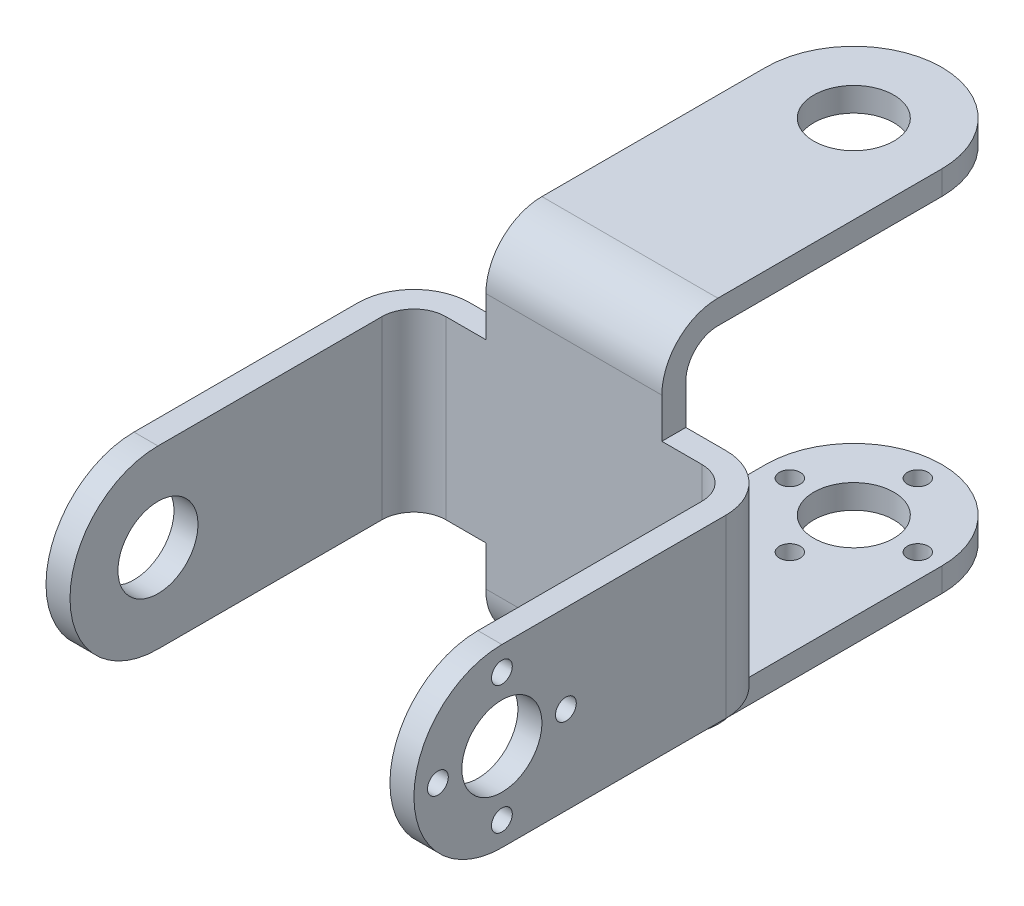
SolidWorks part; units mm, degrees
ref_plane "Front Plane" through (0, 0, 0) normal (0, 0, 1) x (1, 0, 0)
ref_plane "Top Plane" through (0, 0, 0) normal (0, 1, 0) x (1, 0, 0)
ref_plane "Right Plane" through (0, 0, 0) normal (1, 0, 0) x (0, 0, -1)
sketch "Sketch1" plane through (0, 0, 0) normal (0, 1, 0) x (1, 0, 0)
  line L1 (-11, 0) -> (11, 0)
  line L2 (-11, 0) -> (-11, -28)
  line L3 (-11, -28) -> (11, -28)
  line L4 (11, 0) -> (11, -28)
  circle A0 centre (0, 0) radius 11
  circle A2 centre (0, 0) radius 5
  dimension "D3" = 22
  dimension "D4" = 10
  dimension "D5" = 28
extrude "Boss-Extrude1" add sketch "Sketch1" along normal blind 3 contours L1 A2 A0 | L1 A0 A2 | A0 L2 L3 L4 region at (0, 0, -5.3317) region at (0, 0, 5.3317) region at (0, 0, 18.164)
sketch "Sketch2" plane through (11, 0, 0) normal (1, 0, 0) x (0, 0, -1)
  line L0 (-28, 3) -> (-28, 0)
  line L6 (-26.9205, -40) -> (-26.9205, -43.0638)
  line L7 (-35, -4) -> (-32, -4)
  line L8 (-35, -4) -> (-35, -36)
  line L9 (-35, -36) -> (-32, -36)
  line L10 (-32, -4) -> (-32, -36)
  arc A0 (-28, 0) -> (-32, -4) centre (-28, -4) ccw
  arc A1 (-28, 3) -> (-35, -4) centre (-28, -4) ccw
  arc A4 (-32, -36) -> (-26.9205, -40) centre (-28.0028, -36.1492) ccw
  arc A5 (-35, -36) -> (-26.9205, -43.0638) centre (-28.0028, -36.1492) ccw
  line M4 (-28, 3) -> (-28, 0)
  dimension "D1" = 4
  dimension "D2" = 4
  dimension "D3" = 4
  dimension "D4" = 4
  dimension "D5" = 32
extrude "Boss-Extrude2" add sketch "Sketch2" against normal up to surface (22 mm away) contours A1 L7 M4 | L7 | L6 region at (11, -0.4118, 31.5882) region at (11, -20, 33.5) region at (11, -39.8883, 31.1636) up to face at (-11, 1.5, 14)
ref_plane "Plane1" through (0, -40, 0) normal (0, -1, 0) x (-1, 0, 0)
sketch "Sketch3" plane through (0, -40, 0) normal (0, -1, 0) x (-1, 0, 0)
  line L1 (-11, 0) -> (11, 0)
  line L2 (-11, 0) -> (-11, -28)
  line L3 (-11, -28) -> (11, -28)
  line L4 (11, 0) -> (11, -28)
  circle A0 centre (0, 0) radius 5
  circle A1 centre (0, 0) radius 11
  circle A2 centre (0, 0) radius 8 construction
  circle A3 centre (0, 8) radius 1.3
  circle A4 centre (8, 0) radius 1.3
  circle A5 centre (0, -8) radius 1.3
  circle A6 centre (-8, 0) radius 1.3
  dimension "D1" = 16
  dimension "D2" = 2.6
extrude "Boss-Extrude3" add sketch "Sketch3" along normal blind 3 contours A1 L2 L3 L4 | L1 A1 A0 | L1 A1 A0 region at (0, -40, -5.4117) region at (0, -40, 5.4117) region at (0, -40, 18.164)
sketch "Sketch5" plane through (0, 0, 35) normal (0, 0, 1) x (1, 0, 0)
  line L0 (-11, -4) -> (11, -4) construction
  line L5 (-11, -36) -> (11, -36) construction
  line L6 (-11, -36) -> (-11, -4) construction
  line L7 (-11, -20) -> (11, -20) construction
  line L8 (11, -4) -> (11, -36) construction
  line L9 (0, -4) -> (0, -36) construction
  line L11 (-16, -9) -> (16, -9)
  line L12 (-16, -9) -> (-16, -31)
  line L13 (-16, -31) -> (16, -31)
  line L14 (16, -9) -> (16, -31)
  line L15 (-16, -9) -> (16, -31) construction
  line L16 (-16, -31) -> (16, -9) construction
  point P0 (0, -20)
  dimension "D1" = 32
  dimension "D2" = 22
extrude "Boss-Extrude4" add sketch "Sketch5" against normal up to surface (3 mm away) up to face at (0, -20, 32)
sketch "Sketch6" plane through (0, -9, 0) normal (0, 1, 0) x (1, 0, 0)
  line L0 (-23, -39) -> (-20, -39)
  line L1 (20, -39) -> (23, -39)
  line L2 (-16, -35) -> (-16, -32)
  line L3 (16, -32) -> (16, -35)
  arc A0 (-16, -35) -> (-20, -39) centre (-16, -39) ccw
  arc A1 (-16, -32) -> (-23, -39) centre (-16, -39) ccw
  arc A2 (16, -35) -> (20, -39) centre (16, -39) cw
  arc A3 (16, -32) -> (23, -39) centre (16, -39) cw
  dimension "D1" = 4
  dimension "D2" = 4
  dimension "D3" = 4
  dimension "D4" = 4
extrude "Boss-Extrude5" add sketch "Sketch6" against normal up to surface (22 mm away) up to face at (13.5, -31, 33.5)
ref_plane "Plane2" through (23, 0, 0) normal (-1, 0, 0) x (0, 0, 1)
sketch "Sketch8" plane through (23, 0, 0) normal (-1, 0, 0) x (0, 0, 1)
  line L1 (39, -9) -> (67, -9)
  line L2 (39, -9) -> (39, -31)
  line L3 (39, -31) -> (67, -31)
  line L4 (67, -9) -> (67, -31)
  circle A0 centre (67, -20) radius 11
  circle A1 centre (67, -20) radius 8 construction
  circle A2 centre (67, -20) radius 5
  circle A3 centre (59, -20) radius 1.3
  circle A4 centre (67, -28) radius 1.3
  circle A5 centre (75, -20) radius 1.3
  circle A6 centre (67, -12) radius 1.3
  dimension "D2" = 2.6
  dimension "D3" = 10
  dimension "D4" = 16
  dimension "D5" = 22
  dimension "D1" = 28
extrude "Boss-Extrude8" add sketch "Sketch8" along normal blind 3 contours A0 L1 L2 L3 | A6 L4 A0 A4 A2 A3 | A6 L4 A2 A4 A0 A5 region at (23, -20, 48.836) region at (23, -20, 72.4117) region at (23, -20, 61.5883)
ref_plane "Plane3" through (-23, 0, 0) normal (-1, 0, 0) x (0, 0, 1)
sketch "Sketch9" plane through (-23, 0, 0) normal (-1, 0, 0) x (0, 0, 1)
  line L1 (39, -31) -> (67, -31)
  line L2 (39, -31) -> (39, -9)
  line L3 (39, -9) -> (67, -9)
  line L4 (67, -31) -> (67, -9)
  circle A0 centre (67, -20) radius 11
  circle A1 centre (67, -20) radius 5
  dimension "D2" = 22
  dimension "D3" = 10
  dimension "D1" = 28
extrude "Boss-Extrude9" add sketch "Sketch9" against normal blind 3 contours A0 L3 L2 L1 | A1 L4 A0 | A1 L4 A0 region at (-23, -20, 48.836) region at (-23, -20, 61.6683) region at (-23, -20, 72.3317)
